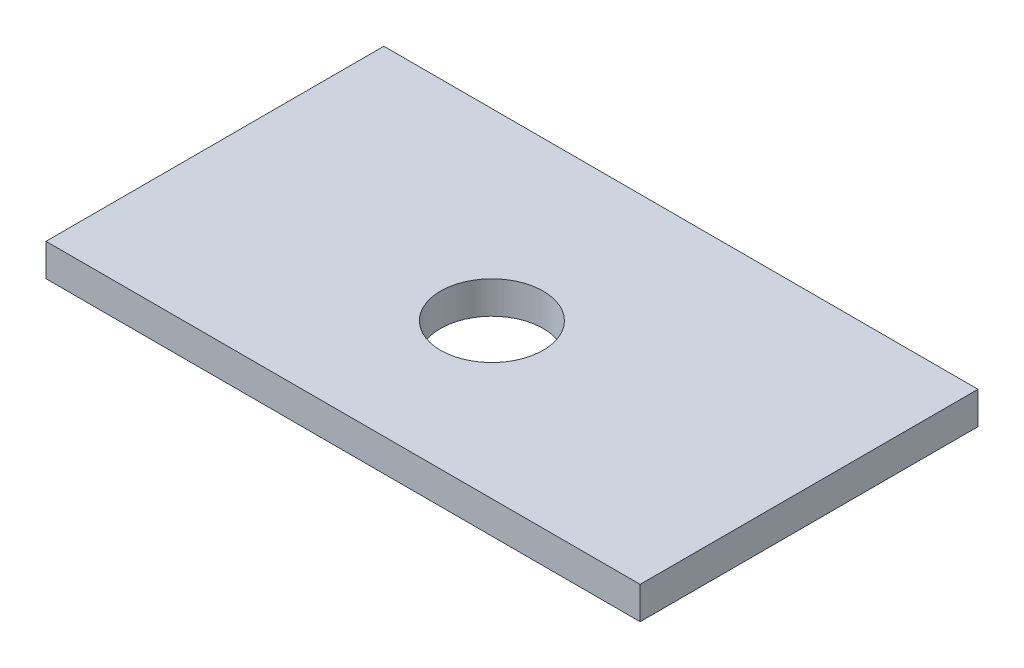
SolidWorks part; units mm, degrees
ref_plane "Front Plane" through (0, 0, 0) normal (0, 0, 1) x (1, 0, 0)
ref_plane "Top Plane" through (0, 0, 0) normal (0, 1, 0) x (1, 0, 0)
ref_plane "Right Plane" through (0, 0, 0) normal (1, 0, 0) x (0, 0, -1)
sketch "Sketch1" plane through (0, 0, 0) normal (0, 1, 0) x (1, 0, 0)
  line L1 (-55, -31.275) -> (55, -31.275)
  line L2 (-55, -31.275) -> (-55, 31.275)
  line L3 (-55, 31.275) -> (55, 31.275)
  line L4 (55, -31.275) -> (55, 31.275)
  line L5 (-55, -31.275) -> (55, 31.275) construction
  line L6 (-55, 31.275) -> (55, -31.275) construction
  point P0 (0, 0)
  dimension "D1" = 62.55
  dimension "D2" = 110
extrude "Boss-Extrude1" add sketch "Sketch1" along normal blind 6
sketch "Sketch2" plane through (0, 6, 0) normal (0, 1, 0) x (1, 0, 0)
  line L0 (-1, 31.275) -> (-1, -31.275) construction
  line L1 (55, 31.275) -> (-55, 31.275) construction
  line L2 (-55, -31.275) -> (55, -31.275) construction
  line L3 (-55, -2.725) -> (55, -2.725) construction
  line L4 (-55, 31.275) -> (-55, -31.275) construction
  line L5 (55, -31.275) -> (55, 31.275) construction
  circle A0 centre (-1, -2.725) radius 9.5
  dimension "D1" = 19
  dimension "D2" = 56
  dimension "D3" = 34
extrude "Cut-Extrude1" cut sketch "Sketch2" against normal up to next
ref_axis "Axis1" through (-1, 0, 2.725) along (0, 1, 0)
